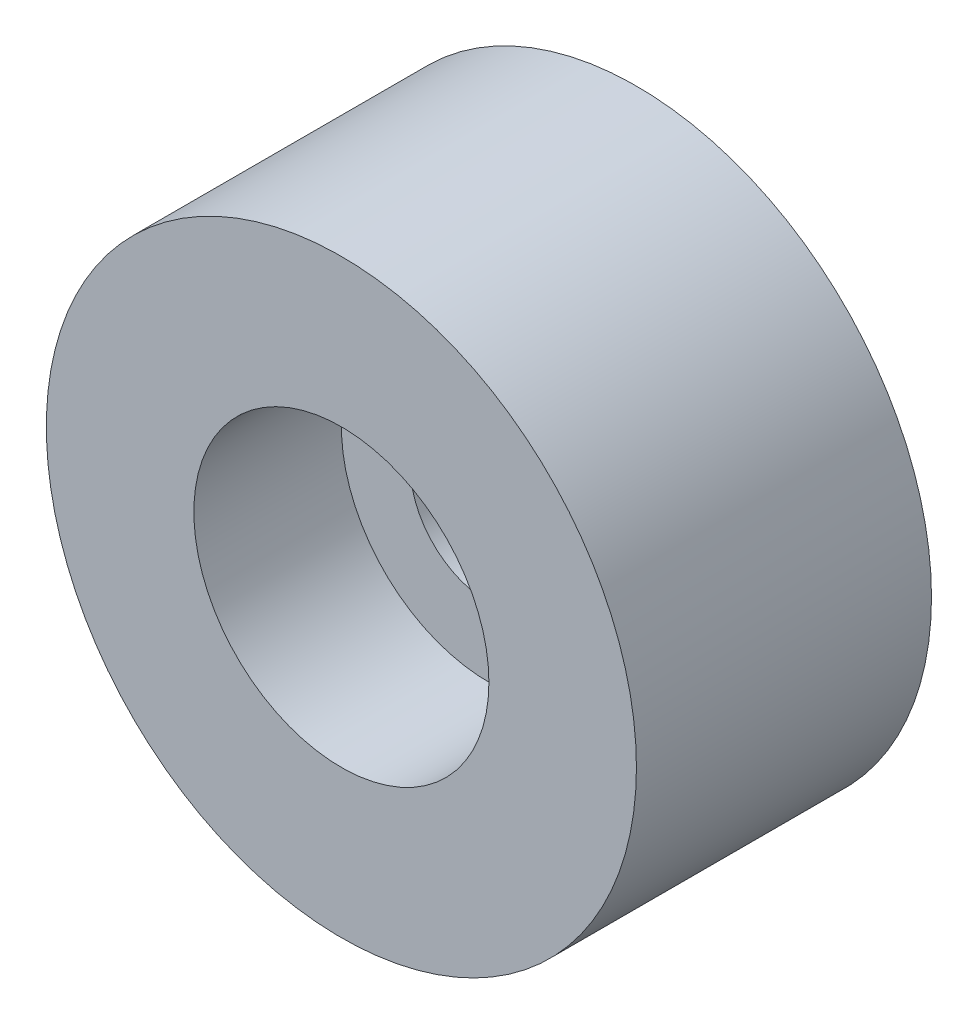
SolidWorks part; units mm, degrees
material "3.1325 (EN-AW 2017A)"
ref_plane "正面" through (0, 0, 0) normal (0, 0, 1) x (1, 0, 0)
ref_plane "平面" through (0, 0, 0) normal (0, 1, 0) x (1, 0, 0)
ref_plane "右側面" through (0, 0, 0) normal (1, 0, 0) x (0, 0, -1)
sketch "ｽｹｯﾁ1" plane through (0, 0, 0) normal (0, 0, 1) x (1, 0, 0)
  circle A0 centre (0, 0) radius 6
  circle A1 centre (0, 0) radius 3
  dimension "D1" = 12
  dimension "D2" = 6
extrude "ﾎﾞｽ - 押し出し1" add sketch "ｽｹｯﾁ1" against normal blind 6 contours A0
extrude "ｶｯﾄ - 押し出し2" cut sketch "ｽｹｯﾁ1<4>" against normal blind 3 contours A1
sketch "ｽｹｯﾁ1<4>" plane through (0, 0, 0) normal (0, 0, 1) x (1, 0, 0) same geometry as "ｽｹｯﾁ1"
hole_wizard "M3 すきま穴1" positions "3Dｽｹｯﾁ1" profile "ｽｹｯﾁ2" hole size "M3" standard "JIS" end condition through all
sketch3d "3Dｽｹｯﾁ1"
  point P0 (0, 0, -6)
sketch "ｽｹｯﾁ2" plane through (0, 0, -6) normal (1, 0, 0) x (0, 1, 0)
  line L0 (0, 0) -> (0, 6)
  line L1 (0, 6) -> (1.6, 6)
  line L2 (1.6, 6) -> (1.6, 0)
  line L5 (1.6, 0) -> (0, 0)
  line L11 (0, -6.35) -> (0, 107.95) construction
  dimension "通し穴の直径" = 3.2
  dimension "通し穴の深さ" = 6
